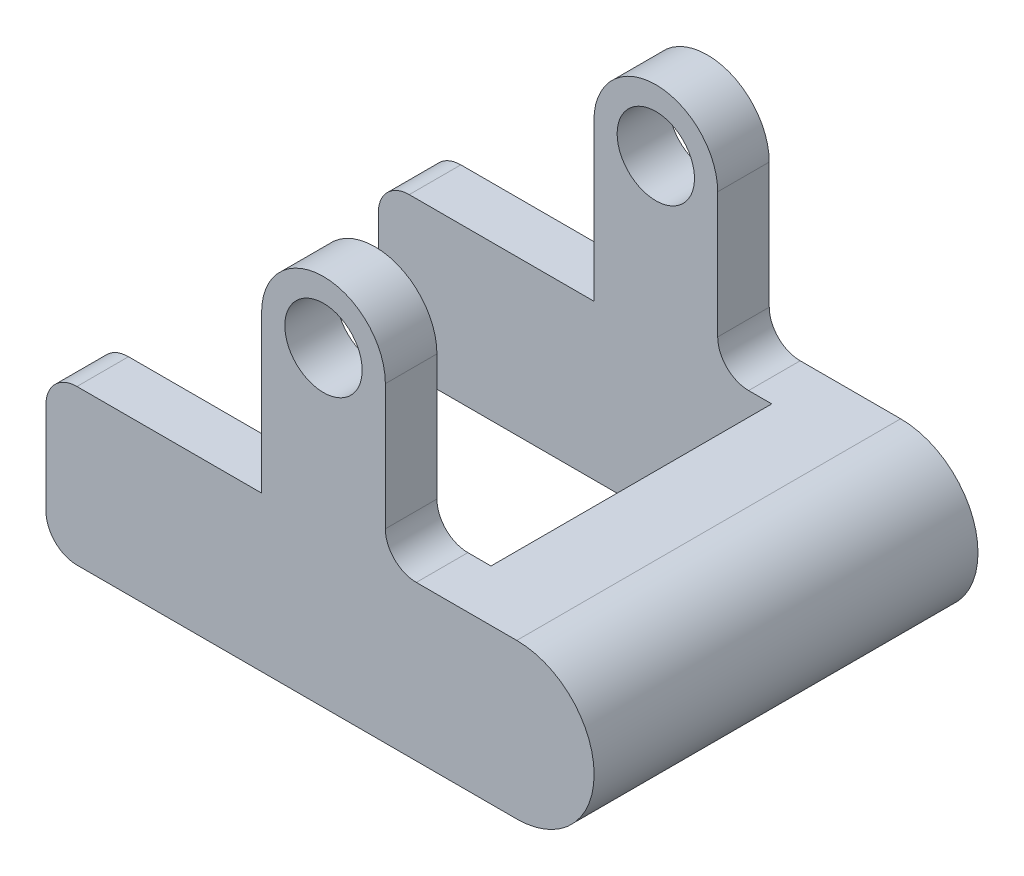
SolidWorks part; units mm, degrees
material "ABS"
ref_plane "Front Plane" through (0, 0, 0) normal (0, 0, 1) x (1, 0, 0)
ref_plane "Top Plane" through (0, 0, 0) normal (0, 1, 0) x (1, 0, 0)
ref_plane "Right Plane" through (0, 0, 0) normal (1, 0, 0) x (0, 0, -1)
sketch "Sketch1" plane through (0, 0, 0) normal (0, 0, 1) x (1, 0, 0)
  line L3 (-825, 179.8054) -> (-986.2125, 179.8054)
  line L4 (-986.2125, 330.75) -> (-986.2125, 179.8054)
  line L5 (-986.2125, 179.8054) -> (-1090.75, 179.8054)
  line L6 (-986.2125, 179.8054) -> (-986.2125, 254.8054)
  line L7 (-986.2125, 254.8054) -> (-1090.75, 254.8054)
  line L8 (-1090.75, 179.8054) -> (-1090.75, 254.8054)
  line L10 (-986.2125, -935.75) -> (-986.2125, 935.75) construction
  line L11 (-990.75, -935.75) -> (-990.75, 935.75) construction
  line L13 (-926.2125, 330.75) -> (-926.2125, 254.8054)
  line L14 (-945.75, 254.8054) -> (945.75, 254.8054) construction
  line L15 (-926.2125, 254.8054) -> (-825, 254.8054)
  line L16 (-825, 254.8054) -> (-825, 179.8054)
  line L17 (-900, -935.75) -> (-900, 935.75) construction
  line L18 (-956.2125, 360.75) -> (-956.2125, 179.8054) construction
  circle A0 centre (-956.2125, 330.75) radius 18.75 construction
  circle A1 centre (-956.2125, 330.75) radius 18.75
  circle A2 centre (-956.2125, 330.75) radius 30 construction
  arc A3 (-926.2125, 330.75) -> (-986.2125, 330.75) centre (-956.2125, 330.75) ccw
  dimension "D1" = 30
  dimension "D2" = 75
  dimension "D3" = 75
  dimension "D5" = 100
extrude "Boss-Extrude1" add sketch "Sketch1" along normal blind 25 contours A1 L3 | L4 L3 A1 | L8 L5 L4 L7 region at (-920.1282, 240.7169, 0) region at (-1038.4813, 217.3054, 0)
sketch "Sketch2" plane through (0, 0, -136.125) normal (0, 0, -1) x (-1, 0, 0)
  line L7 (926.2125, 330.75) -> (926.2125, 254.8054)
  line L8 (926.2125, 254.8054) -> (825, 254.8054)
  line L9 (825, 254.8054) -> (825, 179.8054)
  line L10 (825, 179.8054) -> (1090.75, 179.8054)
  line L11 (1090.75, 179.8054) -> (1090.75, 254.8054)
  line L12 (1090.75, 254.8054) -> (986.2125, 254.8054)
  line L13 (986.2125, 254.8054) -> (986.2125, 330.75)
  line L14 (926.2125, 330.75) -> (926.2125, 254.8054)
  line L15 (926.2125, 254.8054) -> (825, 254.8054)
  line L16 (825, 254.8054) -> (825, 179.8054)
  line L17 (825, 179.8054) -> (1090.75, 179.8054)
  line L18 (1090.75, 179.8054) -> (1090.75, 254.8054)
  line L19 (1090.75, 254.8054) -> (986.2125, 254.8054)
  line L20 (986.2125, 254.8054) -> (986.2125, 330.75)
  circle A0 centre (956.2125, 330.75) radius 18.75 construction
  arc A1 (986.2125, 330.75) -> (926.2125, 330.75) centre (956.2125, 330.75) ccw
  arc A2 (986.2125, 330.75) -> (926.2125, 330.75) centre (956.2125, 330.75) ccw
  circle A3 centre (956.2125, 330.75) radius 18.75
  dimension "D1" = 0
extrude "Boss-Extrude2" add sketch "Sketch2" along normal blind 25 separate body
sketch "Sketch3" plane through (0, 0, -136.125) normal (0, 0, 1) x (1, 0, 0)
  line L0 (-926.2125, 254.8054) -> (-825, 254.8054) construction
  line L1 (-825, 179.8054) -> (-900, 179.8054)
  line L2 (-825, 179.8054) -> (-825, 254.8054)
  line L3 (-825, 254.8054) -> (-900, 254.8054)
  line L4 (-900, 179.8054) -> (-900, 254.8054)
  line L5 (-900, -935.75) -> (-900, 935.75) construction
extrude "Boss-Extrude3" add sketch "Sketch3" along normal up to surface (136.125 mm away) up to face at (-937.4625, 330.75, 0)
fillet "Fillet1" 2 edges at (-825, 254.8054, -68.0625) (-825, 179.8054, -68.0625) type full round first side face at (-894.3562, 254.8054, -68.0625) second side face at (-976.625, 179.8054, -68.0625) middle face at (-825, 217.3054, -68.0625)
fillet "Fillet2" radius 15 6 edges at (-1090.75, 254.8054, -148.625) (-1090.75, 179.8054, -148.625) (-1090.75, 179.8054, 12.5) (-1090.75, 254.8054, 12.5) (-926.2125, 254.8054, -148.625) (-926.2125, 254.8054, 12.5)
